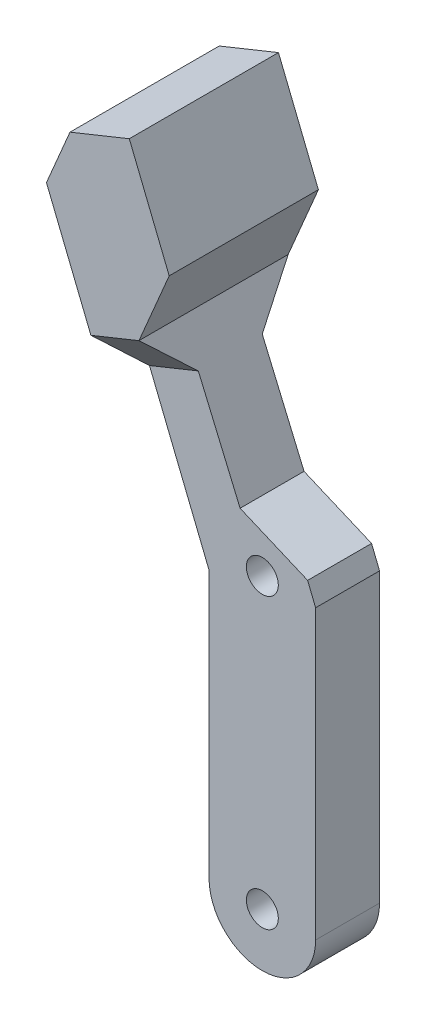
SolidWorks part; units mm, degrees
material "Vero PureWhite"
ref_plane "前视基准面" through (0, 0, 0) normal (0, 0, 1) x (1, 0, 0)
ref_plane "上视基准面" through (0, 0, 0) normal (0, 1, 0) x (1, 0, 0)
ref_plane "右视基准面" through (0, 0, 0) normal (1, 0, 0) x (0, 0, -1)
other "Configuration Table"
sketch "草图1" plane through (0, 0, 0) normal (0, 0, 1) x (1, 0, 0)
  line L0 (0, 0) -> (0, 27) construction
  line L1 (-5, 0) -> (-5, 25.0562)
  line L2 (5, 0) -> (5, 27)
  line L3 (5, 27) -> (4.2508, 28.8544)
  line L4 (4.2508, 28.8544) -> (-2.0859, 31.5441)
  line L5 (-2.0859, 31.5441) -> (-7.5772, 44.4222)
  line L6 (-7.5772, 44.4222) -> (-4.7398, 51.1068)
  line L7 (-8.4858, 60.3786) -> (-17.7577, 56.6326)
  line L8 (-17.7577, 56.6326) -> (-5, 25.0562)
  line L9 (-4.7398, 51.1068) -> (-8.4858, 60.3786)
  arc A0 (-5, 0) -> (5, 0) centre (0, 0) ccw
  point P3 (0, 13.5)
  dimension "D3" = 158
  dimension "D1" = 10
  dimension "D2" = 27
  dimension "D4" = 45
  dimension "D5" = 14
  dimension "D6" = 45
  dimension "D7" = 10
  dimension "D8" = 90
  dimension "D9" = 10
  dimension "D10" = 36
  dimension "D11" = 2
extrude "凸台-拉伸1" add sketch "草图1" along normal blind 6
chamfer "倒角1" distance 4 angle 45 1 edges at (-17.7577, 56.6326, 3)
sketch "草图2" plane through (0, 0, 6) normal (0, 0, 1) x (1, 0, 0)
  line L0 (0, 27.0886) -> (0, 0) construction
  circle A0 centre (0, 27.0886) radius 1.5
  circle A1 centre (0, 0) radius 1.5
  dimension "D1" = 3
  dimension "D2" = 3
extrude "切除-拉伸1" cut sketch "草图2" against normal through all
sketch "草图3" plane through (0, 0, 0) normal (0, 0, -1) x (-1, 0, 0)
  line L0 (16.2592, 52.9238) -> (14.0489, 58.131) construction
  line L1 (8.4858, 60.3786) -> (14.0489, 58.131) construction
  line L2 (4.7398, 51.1068) -> (8.4858, 60.3786) construction
  line L3 (7.5772, 44.4222) -> (4.7398, 51.1068) construction
  line L4 (16.2592, 52.9238) -> (14.0489, 58.131)
  line L5 (8.4858, 60.3786) -> (14.0489, 58.131)
  line L6 (4.7398, 51.1068) -> (8.4858, 60.3786)
  line L7 (7.5772, 44.4222) -> (4.7398, 51.1068)
  line L8 (7.5772, 44.4222) -> (12.088, 42.5997)
  line L9 (16.2592, 52.9238) -> (5, 25.0562) construction
  line L10 (12.088, 42.5997) -> (16.2592, 52.9238)
extrude "凸台-拉伸2" add sketch "草图3" along normal blind 4 and the other way blind 10
chamfer "倒角2" distance 4 angle 45 2 edges at (-9.8326, 43.511, 6) (-9.8326, 43.511, 0)
